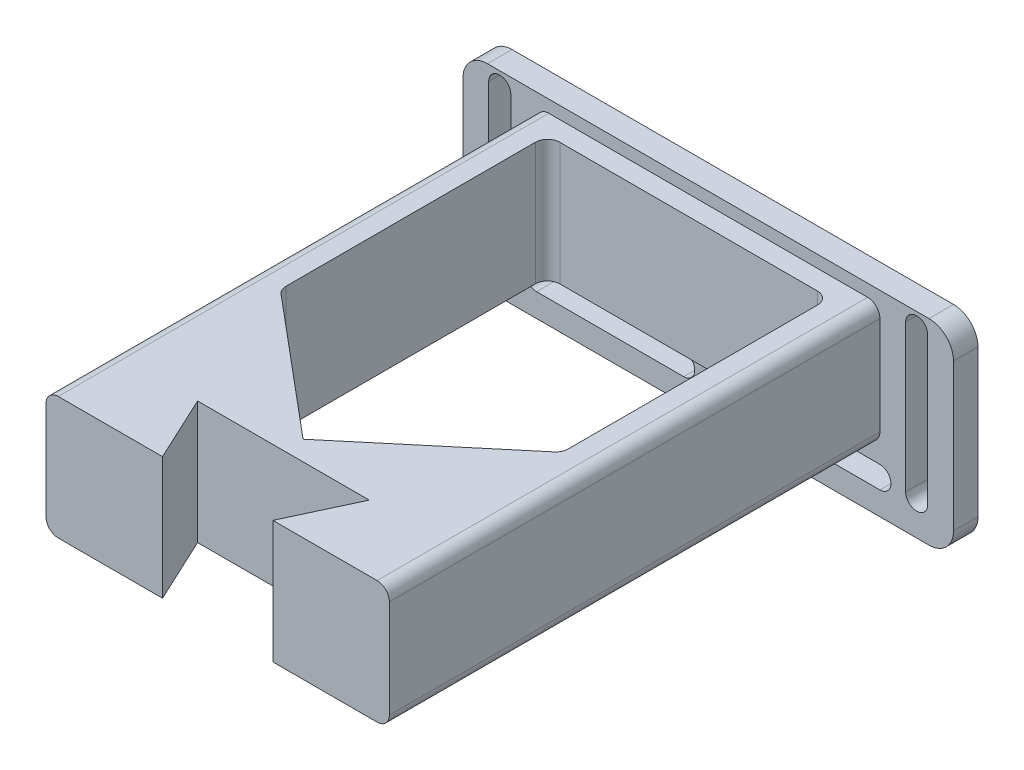
SolidWorks part; units mm, degrees
ref_plane "Front Plane" through (0, 0, 0) normal (0, 0, 1) x (1, 0, 0)
ref_plane "Top Plane" through (0, 0, 0) normal (0, 1, 0) x (1, 0, 0)
ref_plane "Right Plane" through (0, 0, 0) normal (1, 0, 0) x (0, 0, -1)
sketch "Sketch1" plane through (0, 0, 0) normal (0, 0, 1) x (1, 0, 0)
  line L1 (50, -20) -> (-50, -20)
  line L2 (50, -20) -> (50, 20)
  line L3 (50, 20) -> (-50, 20)
  line L4 (-50, -20) -> (-50, 20)
  line L5 (50, -20) -> (-50, 20) construction
  line L6 (50, 20) -> (-50, -20) construction
  point P0 (0, 0)
  dimension "D1" = 40
  dimension "D2" = 100
extrude "Boss-Extrude1" add sketch "Sketch1" along normal blind 5
sketch "Sketch2" plane through (0, 0, 5) normal (0, 0, 1) x (1, 0, 0)
  line L0 (-42.5, 17) -> (-42.5, -13) construction
  line L1 (-40.25, 17) -> (-40.25, -13)
  line L2 (-35, -13) -> (-5, -13) construction
  line L3 (-44.75, 17) -> (-44.75, -13)
  line L7 (42.5, 17) -> (42.5, -13) construction
  line L8 (44.75, 17) -> (44.75, -13)
  line L9 (40.25, 17) -> (40.25, -13)
  line L11 (5, -13) -> (35, -13) construction
  line L12 (5, -10.75) -> (35, -10.75)
  line L13 (5, -15.25) -> (35, -15.25)
  line L14 (-50, -20) -> (50, -20) construction
  line L15 (-50, 20) -> (-50, -20) construction
  line L16 (50, -20) -> (50, 20) construction
  line L17 (-35, -10.75) -> (-5, -10.75)
  line L18 (-35, -15.25) -> (-5, -15.25)
  arc A8 (-40.25, 17) -> (-44.75, 17) centre (-42.5, 17) ccw
  arc A9 (-44.75, -13) -> (-40.25, -13) centre (-42.5, -13) ccw
  arc A10 (44.75, 17) -> (40.25, 17) centre (42.5, 17) ccw
  arc A11 (40.25, -13) -> (44.75, -13) centre (42.5, -13) ccw
  arc A14 (5, -10.75) -> (5, -15.25) centre (5, -13) ccw
  arc A15 (35, -15.25) -> (35, -10.75) centre (35, -13) ccw
  arc A16 (-35, -10.75) -> (-35, -15.25) centre (-35, -13) ccw
  arc A17 (-5, -15.25) -> (-5, -10.75) centre (-5, -13) ccw
  point P2 (-42.5, 2)
  point P7 (-20, -13)
  point P10 (42.5, 2)
  point P21 (20, -13)
  dimension "D7" = 30
  dimension "D1" = 30
  dimension "D2" = 4.5
  dimension "D3" = 30
  dimension "D4" = 4.5
  dimension "D5" = 30
  dimension "D6" = 4.5
  dimension "D8" = 4.5
  dimension "D9" = 7
  dimension "D10" = 7
  dimension "D11" = 7.5
  dimension "D12" = 7.5
  dimension "D13" = 7.5
  dimension "D14" = 7.5
extrude "Cut-Extrude1" cut sketch "Sketch2" against normal blind 5 contours L1 A9 L3 A8
extrude "Cut-Extrude2" cut sketch "Sketch2<3>" against normal blind 5 contours L17 A17 L18 A16
sketch "Sketch2<3>" plane through (0, 0, 5) normal (0, 0, 1) x (1, 0, 0) same geometry as "Sketch2"
extrude "Cut-Extrude3" cut sketch "Sketch2<4>" against normal blind 5 contours L12 A15 L13 A14
sketch "Sketch2<4>" plane through (0, 0, 5) normal (0, 0, 1) x (1, 0, 0) same geometry as "Sketch2"
extrude "Cut-Extrude4" cut sketch "Sketch2<5>" against normal blind 5 contours L9 A11 L8 A10
sketch "Sketch2<5>" plane through (0, 0, 5) normal (0, 0, 1) x (1, 0, 0) same geometry as "Sketch2"
sketch "Sketch3" plane through (0, 0, 5) normal (0, 0, 1) x (1, 0, 0)
  line L0 (50, 20) -> (-50, 20) construction
  line L1 (35, -7.5) -> (-35, -7.5)
  line L2 (35, -7.5) -> (35, 17.5)
  line L3 (35, 17.5) -> (-35, 17.5)
  line L4 (-35, -7.5) -> (-35, 17.5)
  line L5 (35, -7.5) -> (-35, 17.5) construction
  line L6 (35, 17.5) -> (-35, -7.5) construction
  point P0 (0, 5)
  point P5 (0, 0)
  point P8 (0, 20)
  point P9 (30.3874, -7.0599)
  dimension "D1" = 25
  dimension "D2" = 70
  dimension "D3" = 2.5
extrude "Boss-Extrude2" add sketch "Sketch3" along normal blind 100
fillet "Fillet1" radius 5 4 edges at (-50, 20, 2.5) (50, 20, 2.5) (50, -20, 2.5) (-50, -20, 2.5)
fillet "Fillet2" radius 2.5 4 edges at (-35, 17.5, 55) (35, 17.5, 55) (35, -7.5, 55) (-35, -7.5, 55)
sketch "Sketch5" plane through (0, -7.5, 0) normal (0, -1, 0) x (1, 0, 0)
  line L0 (-11.25, 105) -> (-17.5, 91.5968)
  line L1 (-32.5, 105) -> (32.5, 105) construction
  line L2 (-17.5, 91.5968) -> (17.5, 91.5968)
  line L3 (17.5, 91.5968) -> (11.25, 105)
  line L4 (-11.25, 105) -> (-35, 105) construction
  line L5 (11.25, 105) -> (35, 105) construction
  line L6 (-11.25, 105) -> (11.25, 105)
  dimension "D1" = 115
  dimension "D2" = 115
  dimension "D3" = 35
  dimension "D4" = 22.5
extrude "Cut-Extrude6" cut sketch "Sketch5" against normal through all and the other way through all contours L0 L2 L3 L6
sketch "Sketch7" plane through (0, -7.5, 0) normal (0, -1, 0) x (1, 0, 0)
  point P5 (0, 49.8533)
  point P8 (0, 8.9344)
  point P11 (-22.8551, 48.5862)
sketch "Sketch8" plane through (0, -7.5, 0) normal (0, -1, 0) x (1, 0, 0)
  line L0 (-28.75, 9) -> (28.75, 9)
  line L1 (28.75, 9) -> (28.75, 63.4727)
  line L2 (-28.75, 9) -> (-28.75, 63.4727)
  line L3 (-28.75, 63.4727) -> (0, 87.5968)
  line L4 (0, 87.5968) -> (28.75, 63.4727)
  line L5 (-32.5, 5) -> (32.5, 5) construction
  line L6 (-17.5, 91.5968) -> (17.5, 91.5968) construction
  point P2 (0, 9)
  point P6 (0, 0)
  point P8 (0, 87.2537)
  point P9 (28.3518, 9.7799)
  point P10 (0, 88.6728)
  dimension "D1" = 50
  dimension "D2" = 4
  dimension "D3" = 4
  dimension "D4" = 57.5
extrude "Cut-Extrude8" cut sketch "Sketch8" against normal through all contours L2 L3 L4 L1 L0
fillet "Fillet3" radius 2.5 4 edges at (28.75, 5, 63.4727) (-28.75, 5, 63.4727) (28.75, 5, 9) (-28.75, 5, 9)
